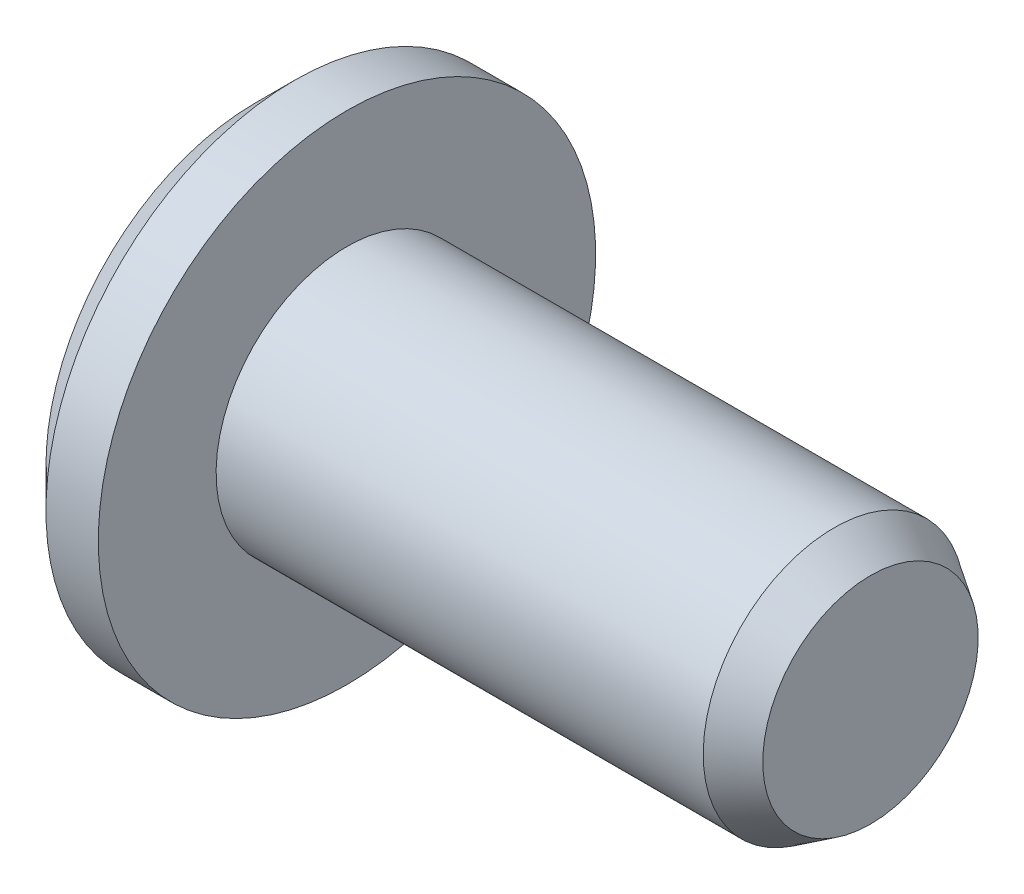
SolidWorks part; units mm, degrees
ref_plane "Front Plane" through (0, 0, 0) normal (0, 0, 1) x (1, 0, 0)
ref_plane "Top Plane" through (0, 0, 0) normal (0, 1, 0) x (1, 0, 0)
ref_plane "Right Plane" through (0, 0, 0) normal (1, 0, 0) x (0, 0, -1)
ref_plane "Plane1" through (5, 0, 0) normal (1, 0, 0) x (0, 0, -1)
sketch "Sketch1" plane through (0, 0, 0) normal (0, 0, 1) x (1, 0, 0)
  line L0 (11.75, 0) -> (11.75, 2.0572)
  line L1 (11.055, 2.5) -> (1.75, 2.5)
  line L2 (1.75, 2.5) -> (1.75, 4.75)
  line L3 (1.75, 4.75) -> (0, 4.75)
  line L4 (0, 0) -> (101.6, 0) construction
  line L7 (11.75, 0) -> (0, 0)
  line L9 (0, 4.75) -> (0, 0)
  line L10 (11.75, 2.0572) -> (11.055, 2.5)
  line L14 (0, 4.75) -> (0, 0) construction
  dimension "D1" = 10
  dimension "D2" = 2.5
  dimension "D3" = 1.75
  dimension "D4" = 122.5
  dimension "D5" = 2.0572
  dimension "D6" = 2.25
revolve "Revolve1" add sketch "Sketch1" angle 360 about L4
sketch "Sketch2" plane through (1.75, 0, 0) normal (1, 0, 0) x (0, 0, -1)
  circle A0 centre (0, 0) radius 2.55
  dimension "D1" = 5.1
curve "Helix/Spiral1" pitch 0.8 height 64 turns 80
sketch "Sketch4" plane through (0, 0, 0) normal (0, 0, 1) x (1, 0, 0)
  line L0 (26.9044, 2.5) -> (26.1244, 2.5)
  line L1 (26.9044, 2.5) -> (26.5079, 2.1165)
  line L2 (26.5079, 2.1165) -> (26.1244, 2.5)
  dimension "D1" = 0.78
  dimension "D2" = 45
  dimension "D3" = 2.5
sweep "Cut-Sweep2" [suppressed] cut profiles "Sketch4" path "Helix/Spiral1"
sketch "Sketch5" plane through (0, 0, 0) normal (-1, 0, 0) x (0, 0, 1)
  line L1 (1.5, -0.866) -> (1.5, 0.866)
  line L2 (1.5, 0.866) -> (0, 1.7321)
  line L3 (0, 1.7321) -> (-1.5, 0.866)
  line L4 (-1.5, 0.866) -> (-1.5, -0.866)
  line L5 (-1.5, -0.866) -> (0, -1.7321)
  line L6 (0, -1.7321) -> (1.5, -0.866)
  circle A0 centre (0, 0) radius 1.5 construction
  dimension "D1" = 3
extrude "Cut-Extrude1" cut sketch "Sketch5" against normal blind 1
chamfer "Chamfer1" distance 0.75 angle 45 1 edges at (0, -4.75, 0)
